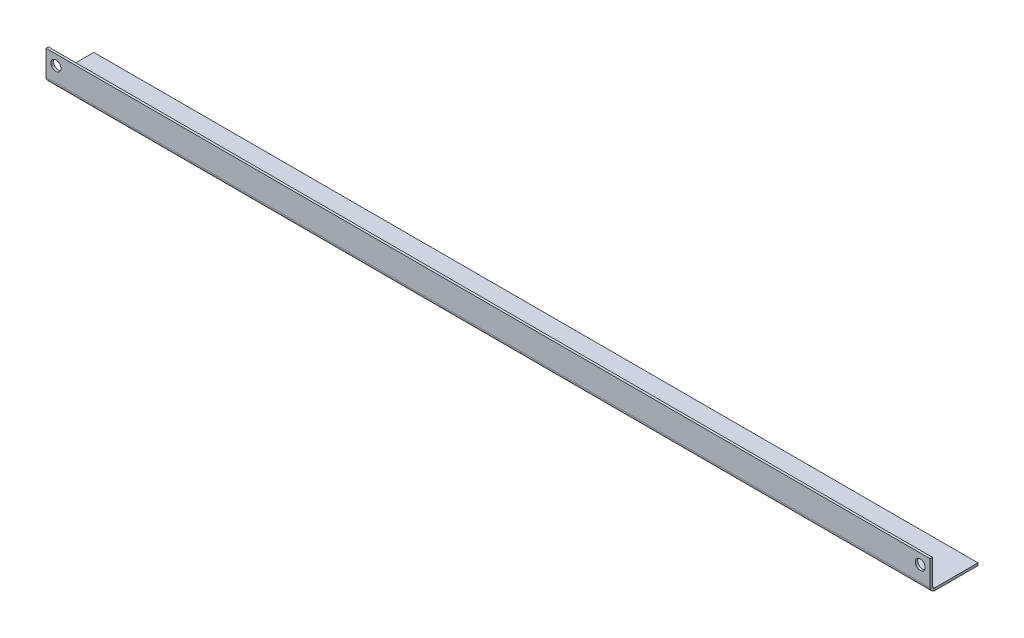
SolidWorks part; units mm, degrees
note: The reader was unsure of these and kept them because the rebuilt part matched: flange length of "Edge-Flange1".
material "1023 Carbon Steel Sheet (SS)"
ref_plane "Front Plane" through (0, 0, 0) normal (0, 0, 1) x (1, 0, 0)
ref_plane "Top Plane" through (0, 0, 0) normal (0, 1, 0) x (1, 0, 0)
ref_plane "Right Plane" through (0, 0, 0) normal (1, 0, 0) x (0, 0, -1)
sketch "Sketch1" plane through (0, 0, 0) normal (0, 1, 0) x (1, 0, 0)
  line L1 (-222, -12) -> (222, -12)
  line L2 (-222, -12) -> (-222, 12)
  line L3 (-222, 12) -> (222, 12)
  line L4 (222, -12) -> (222, 12)
  line L5 (-222, -12) -> (222, 12) construction
  line L6 (-222, 12) -> (222, -12) construction
  point P0 (0, 0)
base flange "Base-Flange1" sketch "Sketch1" thickness 1.214 reverse thickness direction yes parameters "D1"=1
edge flange "Edge-Flange1" sketch "Sketch8" flange angle 90 flange length 15 flange position material inside bend radius 1.214 thickness 1.214 relief rectangular parameters "D6"=10
sketch "Sketch8" plane through (0, 1.214, 12) normal (0, 0, 1) x (1, 0, 0)
  line L0 (-222, 0) -> (222, 0) construction
  line L1 (-222, 0) -> (222, 0)
  line L2 (-222, 0) -> (-222, 13.786)
  line L3 (-222, 13.786) -> (222, 13.786)
  line L4 (222, 13.786) -> (222, 0)
bend "EdgeBend1" bend radius 1.214 bend angle 90 parameters "D5"=1
sketch "Sketch9" plane through (0, 0, 12) normal (0, 0, 1) x (1, 0, 0)
  line L0 (0, 2.428) -> (0, 9.928) construction
  line L1 (222, 2.428) -> (-222, 2.428) construction
  line L2 (0, 9.928) -> (217, 9.928) construction
  line L3 (0, 9.928) -> (-217, 9.928) construction
  circle A0 centre (217, 9.928) radius 2.5
  circle A1 centre (-217, 9.928) radius 2.5
extrude "Cut-Extrude1" cut sketch "Sketch9" against normal blind 10 normal cut yes
sketch "Bend-Lines1" [suppressed] plane through (0, 0, 0) normal (0, 1, 0) x (1, 0, 0)
sketch "Bounding-Box1" [suppressed] plane through (0, 0, 0) normal (0, 1, 0) x (1, 0, 0)
sheet metal parameters "Sheet-Metal1" thickness 1.214 parameters "D1"=1
flat pattern "Flat-Pattern1" [suppressed]
sketch "Bend-Lines2" plane through (0, 0, 0) normal (0, 1, 0) x (1, 0, 0)
sketch3d "Bounding-Box2" [suppressed]
  line L0 (222, 12, 0) -> (-222, 12, 0) construction
  line L1 (222, -12, 0) -> (-222, -12, 0) construction
  line L2 (222, 12, 0) -> (222, -12, 0) construction
  line L3 (-222, 12, 0) -> (-222, -12, 0) construction
sheet metal parameters "Sheet-Metal2" thickness 1.214 parameters "D1"=1
flat pattern "Flat-Pattern1"
sketch "Bend-Lines2" plane through (0, 0, 0) normal (0, -1, 0) x (-1, 0, 0)
  line L0 (-222, -11.0022) -> (222, -11.0022) construction
  line L1 (-222, -11.0022) -> (222, -11.0022) construction
sketch3d "Bounding-Box2" [suppressed]
  line L0 (-222, 12, 0) -> (222, 12, 0) construction
  line L1 (-222, -25.0044, 0) -> (222, -25.0044, 0) construction
  line L2 (-222, 12, 0) -> (-222, -25.0044, 0) construction
  line L3 (222, 12, 0) -> (222, -25.0044, 0) construction
bend of the flat pattern "Flatten-<EdgeBend1>1"
sheet metal parameters "Sheet-Metal3" thickness 1.214 parameters "D1"=1
flat pattern "Flat-Pattern1"
sketch "Bend-Lines2" plane through (0, 0, 0) normal (0, -1, 0) x (-1, 0, 0)
  line L0 (-222, -11.0022) -> (222, -11.0022) construction
  line L1 (-222, -11.0022) -> (222, -11.0022) construction
sketch3d "Bounding-Box2" [suppressed]
  line L0 (-222, 12, 0) -> (222, 12, 0) construction
  line L1 (-222, -25.0044, 0) -> (222, -25.0044, 0) construction
  line L2 (-222, 12, 0) -> (-222, -25.0044, 0) construction
  line L3 (222, 12, 0) -> (222, -25.0044, 0) construction
bend of the flat pattern "Flatten-<EdgeBend1>1"
